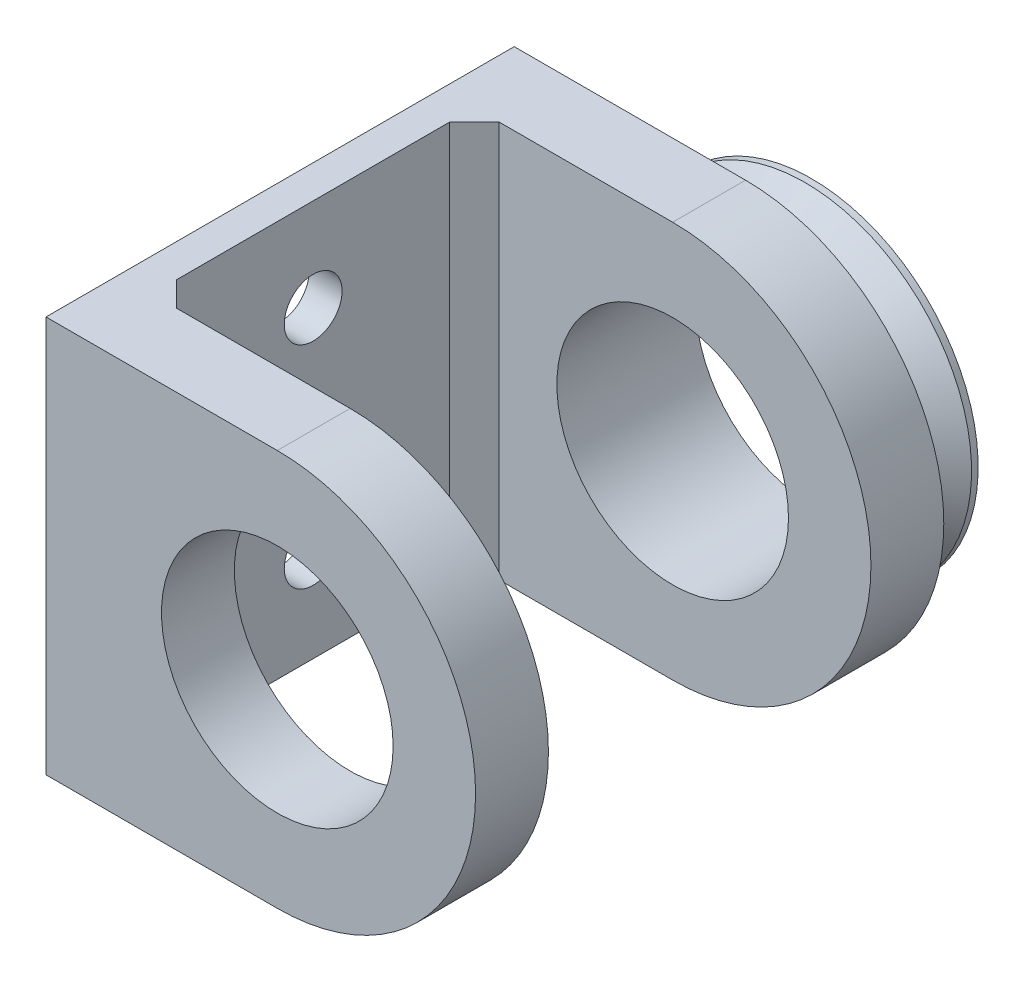
SolidWorks part; units mm, degrees
ref_plane "Front Plane" through (0, 0, 0) normal (0, 0, 1) x (1, 0, 0)
ref_plane "Top Plane" through (0, 0, 0) normal (0, 1, 0) x (1, 0, 0)
ref_plane "Right Plane" through (0, 0, 0) normal (1, 0, 0) x (0, 0, -1)
sketch "Sketch2" plane through (0, 0, 0) normal (0, 0, 1) x (1, 0, 0)
  circle A0 centre (0, 0) radius 10.9982
  dimension "D1" = 21.9964
sketch "Sketch4" plane through (0, 0, 0) normal (0, 0, 1) x (1, 0, 0)
  line L0 (-19.05, 19.05) -> (-19.05, -19.05) construction
  line L1 (-19.05, 19.05) -> (0, 19.05)
  line L2 (-19.05, -19.05) -> (0, -19.05)
  line L3 (-19.05, 19.05) -> (-22.225, 19.05)
  line L4 (-22.225, 19.05) -> (-22.225, -19.05)
  line L5 (-22.225, -19.05) -> (-19.05, -19.05)
  arc A0 (0, -19.05) -> (0, 19.05) centre (0, 0) ccw
  circle A1 centre (0, 0) radius 11.127
  dimension "D1" = 38.1
  dimension "D2" = 22.254
  dimension "D3" = 3.175
extrude "Boss-Extrude1" add sketch "Sketch4" against normal blind 7
extrude "Cut-Extrude1" [suppressed] cut sketch "Sketch2" against normal mid plane 25.4 contours A0
sketch "Sketch6" plane through (0, 0, 0) normal (0, 0, 1) x (1, 0, 0)
  line L0 (-22.225, -19.05) -> (0, -19.05) construction
  line L1 (-22.225, -19.05) -> (-19.05, -19.05)
  line L2 (-22.225, -19.05) -> (-22.225, 19.05)
  line L3 (-22.225, 19.05) -> (-19.05, 19.05)
  line L4 (-19.05, -19.05) -> (-19.05, 19.05)
  line L5 (-22.225, 19.05) -> (-22.225, -19.05) construction
  line L6 (0, 19.05) -> (-22.225, 19.05) construction
  line L7 (-19.05, 19.05) -> (-19.05, -19.05) construction
extrude "Boss-Extrude2" add sketch "Sketch6" along normal blind 15.494
chamfer "Chamfer1" distance 2.38 angle 45 1 edges at (-19.05, 0, 0)
mirror "Mirror1" about plane through (0, 0, 15.494) normal (0, 0, -1) of bodies 103
sketch "Sketch8" plane through (-19.05, 0, 0) normal (1, 0, 0) x (0, 0, -1)
  line L0 (-15.494, 19.05) -> (-15.494, -19.05) construction
  line L1 (-28.608, 19.05) -> (-2.38, 19.05) construction
  line L2 (-28.608, -19.05) -> (-2.38, -19.05) construction
  line L3 (-15.494, 0) -> (-5.0615, 0) construction
  circle A0 centre (-15.494, 10.16) radius 2.7781
  circle A1 centre (-15.494, -10.16) radius 2.7781
  dimension "D1" = 5.5562
  dimension "D2" = 10.16
extrude "Cut-Extrude2" cut sketch "Sketch8" against normal through all
sketch "Sketch9" plane through (0, 0, -7) normal (0, 0, -1) x (-1, 0, 0)
  circle A0 centre (0, 0) radius 11.127 construction
  circle A1 centre (0, 0) radius 11.127
  circle A2 centre (0, 0) radius 16.002
  dimension "D1" = 32.004
extrude "Boss-Extrude3" add sketch "Sketch9" along normal blind 3.175 separate body
chamfer "Chamfer2" distance 2.54 angle 45 1 edges at (-16.002, 0, -10.175)
mirror "Mirror2" about plane through (0, 0, -10.175) normal (0, 0, -1) of bodies 106
combine bodies "Combine1" operation type add bodies to combine 105 107
chamfer "Chamfer3" distance 2.032 angle 15 1 edges at (-16.002, 0, -7) first distance on face at (-16.002, 0, -7)
move or copy body "Body-Move/Copy1" [suppressed] bodies to move or copy 108 parameters "D1"=0, "D2"=0, "D3"=0
